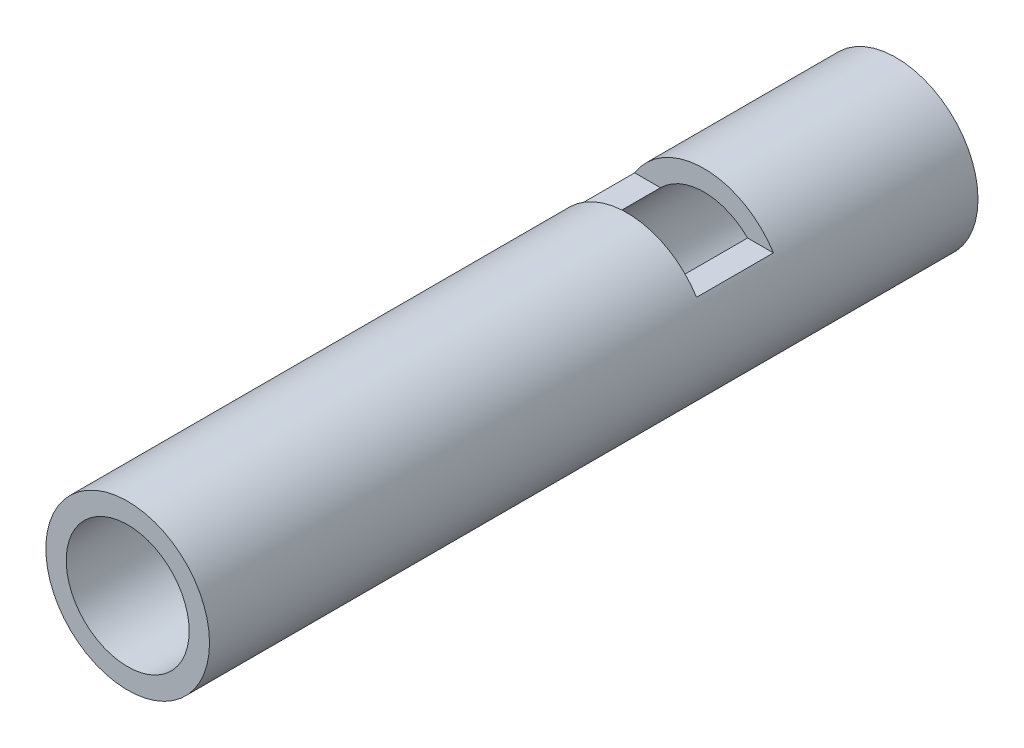
SolidWorks part; units mm, degrees
ref_plane "Ebene vorne" through (0, 0, 0) normal (0, 0, 1) x (1, 0, 0)
ref_plane "Ebene oben" through (0, 0, 0) normal (0, 1, 0) x (1, 0, 0)
ref_plane "Ebene rechts" through (0, 0, 0) normal (1, 0, 0) x (0, 0, -1)
sketch "Skizze1" plane through (0, 0, 0) normal (0, 0, 1) x (1, 0, 0)
  circle A0 centre (0, 0) radius 8
  circle A1 centre (0, 0) radius 10.65
  dimension "D1" = 21.3
  dimension "D2" = 16
extrude "Aufsatz-Linear austragen1" add sketch "Skizze1" along normal blind 100
cosmetic thread "Gewindedarstellung2" parameters "D1"=10, "D2"=18.4887
cosmetic thread "Gewindedarstellung3" parameters "D1"=10, "D2"=18.4887
sketch "Skizze2" plane through (0, 0, 0) normal (1, 0, 0) x (0, 0, -1)
  line L0 (0, 10.65) -> (-100, 10.65) construction
  line L1 (-35, 10.65) -> (-25, 10.65)
  line L2 (-35, 10.65) -> (-35, 5.65)
  line L3 (-35, 5.65) -> (-25, 5.65)
  line L4 (-25, 10.65) -> (-25, 5.65)
  line L5 (0, -10.65) -> (0, 10.65) construction
  dimension "D1" = 25
  dimension "D2" = 35
  dimension "D3" = 5
extrude "Schnitt-Linear austragen1" cut sketch "Skizze2" against normal blind 10 and the other way blind 10
